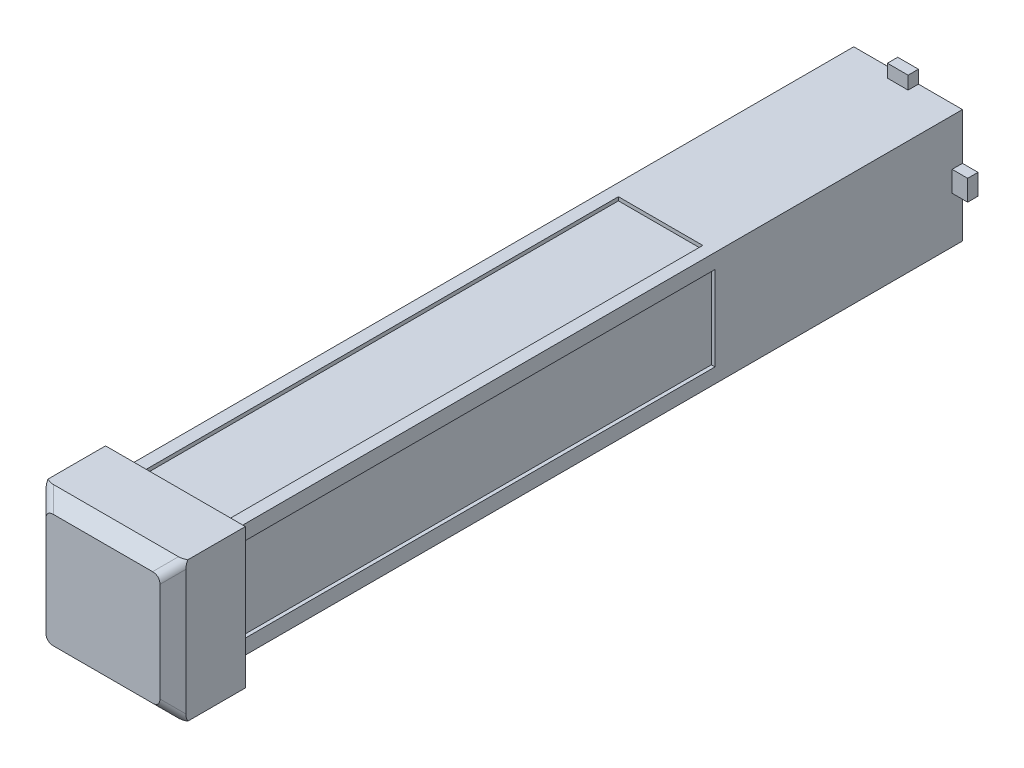
SolidWorks part; units mm, degrees
ref_plane "Front Plane" through (0, 0, 0) normal (0, 0, 1) x (1, 0, 0)
ref_plane "Top Plane" through (0, 0, 0) normal (0, 1, 0) x (1, 0, 0)
ref_plane "Right Plane" through (0, 0, 0) normal (1, 0, 0) x (0, 0, -1)
sketch "Sketch1" plane through (0, 0, 0) normal (0, 0, 1) x (1, 0, 0)
  line L1 (-105, 110) -> (105, 110)
  line L2 (-105, 110) -> (-105, -110)
  line L3 (-105, -110) -> (105, -110)
  line L4 (105, 110) -> (105, -110)
  line L5 (-105, 110) -> (105, -110) construction
  line L6 (-105, -110) -> (105, 110) construction
  point P0 (0, 0)
extrude "Boss-Extrude1" add sketch "Sketch1" along normal blind 1555
sketch "Sketch2" plane through (-105, 0, 0) normal (-1, 0, 0) x (0, 0, 1)
  line L0 (1555, 0) -> (1415, 0) construction
  line L1 (1555, 110) -> (1555, -110) construction
  line L2 (1415, 0) -> (946.5, 0) construction
  line L4 (478, 81.5) -> (1415, 81.5)
  line L5 (478, 81.5) -> (478, -81.5)
  line L6 (478, -81.5) -> (1415, -81.5)
  line L7 (1415, 81.5) -> (1415, -81.5)
  line L8 (478, 81.5) -> (1415, -81.5) construction
  line L9 (478, -81.5) -> (1415, 81.5) construction
  dimension "D1" = 163
  dimension "D2" = 937
  dimension "D3" = 140
extrude "Cut-Extrude1" cut sketch "Sketch2" against normal blind 7
mirror "Mirror2" about plane through (0, 0, 0) normal (1, 0, 0) of "Cut-Extrude1"
sketch "Sketch4" plane through (0, 110, 0) normal (0, 1, 0) x (1, 0, 0)
  line L0 (0, -1555) -> (0, -1415) construction
  line L1 (105, -1555) -> (-105, -1555) construction
  line L2 (0, -1415) -> (0, -946.5) construction
  line L4 (-81.5, -478) -> (81.5, -478)
  line L5 (-81.5, -478) -> (-81.5, -1415)
  line L6 (-81.5, -1415) -> (81.5, -1415)
  line L7 (81.5, -478) -> (81.5, -1415)
  line L8 (-81.5, -478) -> (81.5, -1415) construction
  line L9 (-81.5, -1415) -> (81.5, -478) construction
  dimension "D1" = 937
  dimension "D2" = 140
  dimension "D3" = 163
extrude "Cut-Extrude2" cut sketch "Sketch4" against normal blind 7
mirror "Mirror3" about plane through (0, 0, 0) normal (0, 1, 0) of "Cut-Extrude2"
sketch "Sketch5" plane through (0, 0, 1555) normal (0, 0, 1) x (1, 0, 0)
  line L1 (-135, 135) -> (135, 135)
  line L2 (-135, 135) -> (-135, -135)
  line L3 (-135, -135) -> (135, -135)
  line L4 (135, 135) -> (135, -135)
  line L5 (-135, 135) -> (135, -135) construction
  line L6 (-135, -135) -> (135, 135) construction
  point P0 (0, 0)
extrude "Boss-Extrude2" add sketch "Sketch5" against normal blind 140
chamfer "Chamfer1" distance 25 angle 45 4 edges at (-135, 0, 1555) (0, -135, 1555) (135, 0, 1555) (0, 135, 1555)
fillet "Fillet1" radius 20 4 edges at (-122.5, 122.5, 1542.5) (122.5, 122.5, 1542.5) (122.5, -122.5, 1542.5) (-122.5, -122.5, 1542.5)
sketch "Sketch6" plane through (0, 0, 0) normal (0, 0, -1) x (-1, 0, 0)
  line L0 (135, -135) -> (-135, -135) construction
  line L1 (-20, 135) -> (20, 135)
  line L2 (-20, 135) -> (-20, 20)
  line L3 (-20, -135) -> (20, -135)
  line L4 (20, 135) -> (20, 20)
  line L5 (-20, -20) -> (-20, -135)
  line L6 (20, -20) -> (20, -135)
  line L7 (135, 135) -> (135, -135) construction
  line L8 (-135, 20) -> (-20, 20)
  line L9 (-135, 20) -> (-135, -20)
  line L10 (-135, -20) -> (-20, -20)
  line L11 (135, 20) -> (135, -20)
  line L14 (20, -20) -> (135, -20)
  line L19 (20, 20) -> (135, 20)
  point P0 (0, 0)
  point P8 (0, 0)
extrude "Boss-Extrude3" add sketch "Sketch6" against normal blind 20
ref_point "Point1"
ref_point "Point2"
ref_axis "Axis1" through (0, 0, 1555) along (0, 0, -1)
